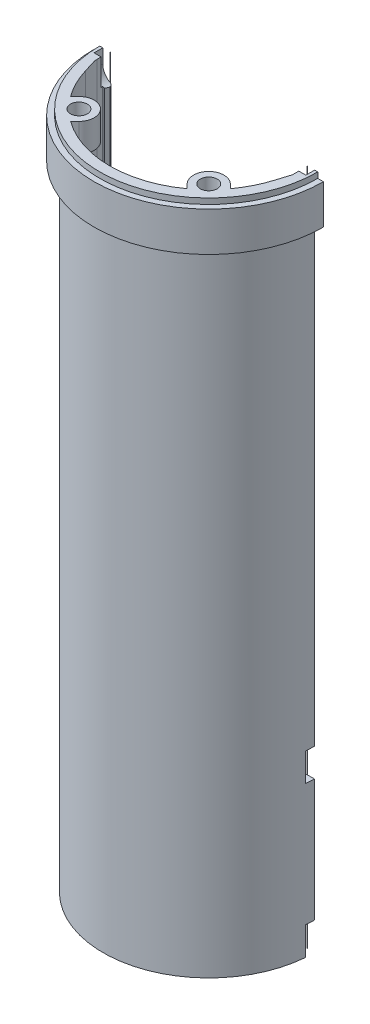
SolidWorks part; units mm, degrees
ref_plane "Front Plane" through (0, 0, 0) normal (0, 0, 1) x (1, 0, 0)
ref_plane "Top Plane" through (0, 0, 0) normal (0, 1, 0) x (1, 0, 0)
ref_plane "Right Plane" through (0, 0, 0) normal (1, 0, 0) x (0, 0, -1)
sketch "Sketch1" plane through (0, 0, 0) normal (0, 0, 1) x (1, 0, 0)
  line L0 (-104.012, -49.1938) -> (-104.012, -164.1938) construction
  line L1 (-136.512, -49.1938) -> (-136.512, -164.1938) construction
  line L2 (-136.512, -49.1938) -> (-104.012, -49.1938) construction
  line L3 (-139.062, -49.1938) -> (-101.462, -49.1938) construction
  line L4 (-101.562, -49.1938) -> (-101.562, -164.1938) construction
  line L5 (-101.562, -164.1938) -> (-101.562, -166.6938) construction
  line L6 (-101.562, -166.6938) -> (-102.762, -166.6938) construction
  line L7 (-136.512, -166.6938) -> (-104.012, -166.6938) construction
  line L8 (-101.562, -166.6938) -> (-102.762, -166.6938)
  line L9 (-101.562, -166.6938) -> (-101.562, -46.6938)
  line L10 (-102.762, -166.6938) -> (-102.762, -46.6938)
  line L11 (-101.562, -46.6938) -> (-102.762, -46.6938)
  line L12 (-104.012, -46.6938) -> (-136.512, -46.6938) construction
  line L13 (-134.9568, -103.2178) -> (-134.9568, -57.1578) construction
  line L14 (-101.562, -46.6938) -> (-99.962, -46.6938)
  line L15 (-101.562, -46.6938) -> (-101.562, -54.6578)
  line L16 (-101.562, -54.6578) -> (-99.962, -54.6578)
  line L17 (-99.962, -46.6938) -> (-99.962, -54.6578)
  line L18 (-134.9568, -86.9728) -> (-134.9568, -73.4028) construction
  line L19 (-134.9568, -86.9728) -> (-134.9568, -73.4028)
  line L20 (-101.562, -109.6578) -> (-99.962, -109.6578) construction
  line L21 (-101.562, -109.6578) -> (-101.562, -166.6938) construction
  line L22 (-99.962, -109.6578) -> (-99.962, -166.6938) construction
  line L23 (-101.562, -166.6938) -> (-99.962, -166.6938) construction
  line L24 (-104.012, -161.6938) -> (-102.762, -161.6938) construction
  line L25 (-104.012, -166.6938) -> (-102.762, -166.6938) construction
  line L29 (-104.012, -166.6938) -> (-102.762, -166.6938)
  circle A0 centre (-136.512, -164.1938) radius 1.1 construction
  circle A1 centre (-104.012, -164.1938) radius 1.1 construction
  circle A2 centre (-104.012, -137.541) radius 1.1 construction
  circle A3 centre (-136.512, -137.541) radius 1.1 construction
  circle A4 centre (-136.512, -49.1938) radius 1.1 construction
  circle A5 centre (-104.012, -49.1938) radius 1.1 construction
  circle A6 centre (-136.512, -164.1938) radius 1.1 construction
  circle A7 centre (-104.012, -164.1938) radius 1.1 construction
  circle A8 centre (-104.012, -137.541) radius 1.1 construction
  circle A9 centre (-136.512, -137.541) radius 1.1 construction
  circle A10 centre (-136.512, -49.1938) radius 1.1 construction
  circle A11 centre (-104.012, -49.1938) radius 1.1 construction
  arc A12 (-104.012, -161.6938) -> (-104.012, -166.6938) centre (-104.012, -164.1938) ccw construction
  arc A13 (-104.012, -166.6938) -> (-104.012, -161.6938) centre (-104.012, -164.1938) ccw construction
  circle A18 centre (-104.012, -164.1938) radius 1.5 construction
  point P18 (-101.562, -49.1938)
  point P21 (-120.262, -49.1938)
  point P39 (-134.9568, -80.1878)
  point P44 (-134.9568, -80.1878)
  dimension "D9" = 3
  dimension "D1" = 37.6
  dimension "D2" = 0.1
  dimension "D3" = 1.2
  dimension "D4" = 2.5
  dimension "D5" = 46.06
  dimension "D6" = 1.6
  dimension "D7" = 55
ref_plane "Plane1" through (0, 0, 0) normal (0, 0, 1) x (1, 0, 0)
sketch "Sketch2" plane through (0, 0, 0) normal (0, 0, 1) x (1, 0, 0)
  line L0 (-120.262, -49.1938) -> (-120.262, -166.1575) construction
ref_axis "Axis1" through (-120.262, -49.1938, 0) along (0, -1, 0)
revolve "Revolve1" add sketch "Sketch1" angle 180 about L0 region at (-102.162, -106.6938, 0) region at (-100.762, -50.6758, 0)
ref_plane "Plane2" through (0, 0, 15) normal (0, 0, 1) x (1, 0, 0)
sketch "Sketch14" plane through (0, 0, 0) normal (0, 0, -1) x (-1, 0, 0)
  line L0 (140.562, -46.6938) -> (140.562, -47.6938)
  line L1 (140.562, -46.6938) -> (139.562, -46.6938)
  line L2 (140.562, -47.6938) -> (139.562, -47.6938)
  line L3 (139.562, -46.6938) -> (139.562, -47.6938)
  line L4 (140.562, -46.6938) -> (140.562, -54.6578) construction
  dimension "D1" = 1
  dimension "D2" = 1
revolve "Cut-Revolve1" cut sketch "Sketch14" angle 360 about L0
ref_plane "Plane3" through (0, -106.6938, 0) normal (0, 1, 0) x (1, 0, 0)
ref_plane "Plane4" through (-120.262, 0, 0) normal (1, 0, 0) x (0, 0, -1)
sketch "Sketch16" plane through (0, -166.6938, 0) normal (0, -1, 0) x (1, 0, 0)
  line L0 (-134.562, 10.0876) -> (-134.562, -3.5283)
  line L1 (-137.762, 0) -> (-136.512, 0)
  line L2 (-136.512, 0) -> (-136.512, 1.25)
  line L3 (-136.512, 1.25) -> (-137.762, 1.25)
  line L4 (-137.762, 1.25) -> (-137.762, 2.2982)
  line L5 (-137.762, 2.2982) -> (-137.762, 2.8996) construction
  line L6 (-137.762, 2.5989) -> (-137.0067, 5.0857) construction
  line L7 (-137.762, 2.8996) -> (-137.762, 2.5989) construction
  line L8 (-137.762, 1.25) -> (-137.762, 0)
  line L9 (-137.0067, 5.0857) -> (-137.137, 1.25)
  arc A0 (-102.762, 0) -> (-137.762, 0) centre (-120.262, 0) ccw construction
  spline S0 degree 3 poles (-137.762, 2.2982) (-137.762, 2.8996) (-137.762, 2.5989) (-137.0067, 5.0857) knots 0 0 0 0 1 1 1 1
  point P5 (-137.762, 0)
  arc M3 (-137.762, 0) -> (-102.762, 0) centre (-120.262, 0) cw
  dimension "D1" = 3.2
  dimension "D2" = 1.2
  dimension "D3" = 1.25
  dimension "D4" = 1.25
extrude "Cut-Extrude1" cut sketch "Sketch16" against normal through all contours L9 L3 M3 | S0 L4 L3 M3 | L3 L8 M3 | L2 L3 L1 M3 region at (-137.1296, -166.6938, 0.6212) region at (-137.7486, -166.6938, 0.9376) region at (-137.5977, -166.6938, 2.7215) region at (-137.311, -166.6938, 2.6601)
sketch "Sketch17" plane through (0, -166.6938, 0) normal (0, -1, 0) x (1, 0, 0)
  line L2 (-137.762, 0) -> (-137.762, 2.2982) construction
  line L3 (-137.262, 0.4943) -> (-137.463, 1.2443)
  line L4 (-137.463, 1.2443) -> (-137.762, 1.2443)
  line L5 (-137.762, 1.2443) -> (-137.762, -0.0057)
  arc A0 (-137.762, -0.0057) -> (-137.262, 0.4943) centre (-137.762, 0.4943) ccw
  dimension "D1" = 0.5
  dimension "D2" = 1.25
  dimension "D3" = 75
extrude "Boss-Extrude1" add sketch "Sketch17" against normal up to surface (120 mm away)
ref_plane "Plane5" through (-120.262, 0, 0) normal (1, 0, 0) x (0, 0, -1)
mirror "Mirror1" about plane through (-120.262, 0, 0) normal (1, 0, 0) of "Cut-Extrude1", "Boss-Extrude1"
sketch "Sketch18" plane through (0, 0, 0) normal (0, 0, -1) x (-1, 0, 0)
  line L0 (139.012, -49.1938) -> (139.012, -46.6938)
  line L1 (136.512, -135.041) -> (138.962, -135.041)
  line L2 (136.512, -140.041) -> (138.962, -140.041)
  line L3 (136.512, -161.6938) -> (138.962, -161.6938)
  line L9 (136.512, -51.6938) -> (136.512, -135.041)
  line L10 (139.562, -46.6938) -> (136.512, -46.6938)
  line L11 (139.562, -47.6938) -> (139.562, -46.6938)
  line L12 (140.562, -47.6938) -> (139.562, -47.6938)
  line L13 (140.562, -54.6578) -> (140.562, -47.6938)
  line L14 (138.962, -54.6578) -> (140.562, -54.6578)
  line L15 (138.962, -166.6938) -> (138.962, -54.6578)
  line L16 (136.512, -166.6938) -> (138.962, -166.6938)
  line L17 (136.512, -140.041) -> (136.512, -161.6938)
  line L18 (136.512, -51.6938) -> (136.512, -135.041)
  line L19 (139.562, -46.6938) -> (136.512, -46.6938)
  line L20 (139.562, -47.6938) -> (139.562, -46.6938)
  line L21 (140.562, -47.6938) -> (139.562, -47.6938)
  line L22 (140.562, -54.6578) -> (140.562, -47.6938)
  line L23 (138.962, -54.6578) -> (140.562, -54.6578)
  line L24 (138.962, -166.6938) -> (138.962, -54.6578)
  line L25 (136.512, -166.6938) -> (138.962, -166.6938)
  line L26 (136.512, -140.041) -> (136.512, -161.6938)
  circle A0 centre (136.512, -49.1938) radius 2.5
  arc A3 (136.512, -135.041) -> (136.512, -140.041) centre (136.512, -137.541) ccw
  arc A4 (136.512, -46.6938) -> (136.512, -51.6938) centre (136.512, -49.1938) ccw
  arc A5 (136.512, -161.6938) -> (136.512, -166.6938) centre (136.512, -164.1938) ccw
  arc A6 (136.512, -135.041) -> (136.512, -140.041) centre (136.512, -137.541) ccw
  arc A7 (136.512, -46.6938) -> (136.512, -51.6938) centre (136.512, -49.1938) ccw
  arc A8 (136.512, -161.6938) -> (136.512, -166.6938) centre (136.512, -164.1938) ccw
  line M15 (139.562, -46.6938) -> (137.762, -46.6938)
  line M16 (137.762, -46.6938) -> (137.762, -166.6938)
  line M17 (137.762, -166.6938) -> (138.962, -166.6938)
  line M18 (138.962, -166.6938) -> (138.962, -54.6578)
  dimension "D1" = 0
extrude "Cut-Extrude2" cut sketch "Sketch18" against normal blind 1.55 contours L3 M16 M17 M18 | L3 A8 L25 M16 | L1 A6 L2 M16 | L2 L1 M16 M18 | A0 M16 | A0 M16 | A0 L0 M15 M16 | A0 L19 M16 region at (-138.566, -47.3039, 0) region at (-138.2746, -49.1938, 0) region at (-136.0837, -49.1938, 0) region at (-137.4538, -46.793, 0) region at (-136.1068, -137.541, 0) region at (-138.362, -137.541, 0) region at (-136.1068, -164.1938, 0) region at (-138.362, -164.1938, 0)
mirror "Mirror2" about plane through (-120.262, 0, 0) normal (1, 0, 0) of "Cut-Extrude2"
sketch "Sketch19" plane through (0, -46.6938, 0) normal (0, 1, 0) x (1, 0, 0)
  line L0 (-106.8623, 9.5813) -> (-106.1266, 10.317) construction
  line L1 (-110.6807, 13.3997) -> (-109.945, 14.1354) construction
  line L2 (-133.6617, 9.5813) -> (-134.3974, 10.317) construction
  line L3 (-129.8433, 13.3997) -> (-130.579, 14.1354) construction
  line L4 (-106.8623, 9.5813) -> (-106.1266, 10.317)
  line L5 (-110.6807, 13.3997) -> (-109.945, 14.1354)
  line L6 (-133.6617, 9.5813) -> (-134.3974, 10.317)
  line L7 (-129.8433, 13.3997) -> (-130.579, 14.1354)
  line L8 (-99.962, 0) -> (-140.562, 0) construction
  line L9 (-129.8433, -13.3997) -> (-130.579, -14.1354)
  line L10 (-133.6617, -9.5813) -> (-134.3974, -10.317)
  line L11 (-110.6807, -13.3997) -> (-109.945, -14.1354)
  line L12 (-106.8623, -9.5813) -> (-106.1266, -10.317)
  arc A0 (-137.0067, -5.0857) -> (-103.5173, -5.0857) centre (-120.262, 0) ccw construction
  arc A1 (-110.6807, 13.3997) -> (-106.8623, 9.5813) centre (-108.7715, 11.4905) ccw construction
  circle A2 centre (-108.7715, 11.4905) radius 1.5 construction
  arc A3 (-133.6617, 9.5813) -> (-129.8433, 13.3997) centre (-131.7525, 11.4905) ccw construction
  circle A4 centre (-131.7525, 11.4905) radius 1.5 construction
  arc A5 (-137.0067, -5.0857) -> (-103.5173, -5.0857) centre (-120.262, 0) ccw
  arc A6 (-110.6807, 13.3997) -> (-106.8623, 9.5813) centre (-108.7715, 11.4905) ccw
  circle A7 centre (-108.7715, 11.4905) radius 1.5
  arc A8 (-133.6617, 9.5813) -> (-129.8433, 13.3997) centre (-131.7525, 11.4905) ccw
  circle A9 centre (-131.7525, 11.4905) radius 1.5
  circle A10 centre (-131.7525, -11.4905) radius 1.5
  arc A11 (-133.6617, -9.5813) -> (-129.8433, -13.3997) centre (-131.7525, -11.4905) cw
  circle A12 centre (-108.7715, -11.4905) radius 1.5
  arc A13 (-110.6807, -13.3997) -> (-106.8623, -9.5813) centre (-108.7715, -11.4905) cw
  arc M6 (-103.5173, -5.0857) -> (-137.0067, -5.0857) centre (-120.262, 0) cw
extrude "Boss-Extrude2" add sketch "Sketch19" against normal blind 5 contours A11 L10 A10 L9 M6 | A13 L11 A12 L12 M6 region at (-110.2594, -46.6938, 13.7141) region at (-130.2646, -46.6938, 13.7141)
sketch "Sketch20" plane through (0, -46.6938, 0) normal (0, 1, 0) x (1, 0, 0)
  arc A0 (-107.2943, -11.7512) -> (-108.5108, -12.9677) centre (-108.7715, -11.4905) ccw construction
  arc A1 (-132.0132, -12.9677) -> (-133.2297, -11.7512) centre (-131.7525, -11.4905) ccw construction
  arc A2 (-107.2943, -11.7512) -> (-108.5108, -12.9677) centre (-108.7715, -11.4905) ccw
  arc A3 (-132.0132, -12.9677) -> (-133.2297, -11.7512) centre (-131.7525, -11.4905) ccw
  circle A4 centre (-131.7525, -11.4905) radius 1.5
  circle A5 centre (-108.7715, -11.4905) radius 1.5
  arc M1 (-108.5108, -12.9677) -> (-107.2943, -11.7512) centre (-108.7715, -11.4905) cw
  arc M2 (-107.2943, -11.7512) -> (-108.5108, -12.9677) centre (-120.262, 0) cw
  arc M23 (-132.0132, -12.9677) -> (-133.2297, -11.7512) centre (-120.262, 0) cw
  arc M24 (-133.2297, -11.7512) -> (-132.0132, -12.9677) centre (-131.7525, -11.4905) cw
extrude "Cut-Extrude3" cut sketch "Sketch20" against normal up to surface (5 mm away) contours A5 M2 | A4 M23 | M23 M24 | M1 M2 region at (-108.8127, -46.6938, 11.4493) region at (-107.8194, -46.6938, 12.4426) region at (-131.7113, -46.6938, 11.4493) region at (-132.7046, -46.6938, 12.4426) up to face at (-108.8707, -51.6938, 11.3913)
ref_plane "Plane6" through (0, -106.6938, 0) normal (0, 1, 0) x (1, 0, 0)
mirror "Mirror3" about plane through (0, -106.6938, 0) normal (0, 1, 0) of "Boss-Extrude2"
sketch "Sketch21" plane through (0, -166.6938, 0) normal (0, -1, 0) x (1, 0, 0)
  arc A0 (-108.5108, 12.9677) -> (-107.2943, 11.7512) centre (-108.7715, 11.4905) ccw construction
  arc A1 (-133.2297, 11.7512) -> (-132.0132, 12.9677) centre (-131.7525, 11.4905) ccw construction
  arc A2 (-108.5108, 12.9677) -> (-107.2943, 11.7512) centre (-108.7715, 11.4905) ccw
  arc A3 (-133.2297, 11.7512) -> (-132.0132, 12.9677) centre (-131.7525, 11.4905) ccw
  circle A4 centre (-131.7525, 11.4905) radius 1.5
  circle A5 centre (-108.7715, 11.4905) radius 1.4772
  arc M19 (-108.5108, 12.9677) -> (-107.2943, 11.7512) centre (-120.262, 0) cw
  arc M20 (-132.0132, 12.9677) -> (-133.2297, 11.7512) centre (-131.7525, 11.4905) cw
  arc M21 (-133.2297, 11.7512) -> (-132.0132, 12.9677) centre (-120.262, 0) cw
extrude "Cut-Extrude4" cut sketch "Sketch21" along direction (0, -1, 0) on the side against the normal blind 5 contours A5 M19 | A5 M19 | M20 M21 | A4 M21 region at (-108.8076, -166.6938, 11.4544) region at (-107.8256, -166.6938, 12.4364) region at (-131.7113, -166.6938, 11.4493) region at (-132.7046, -166.6938, 12.4426)
